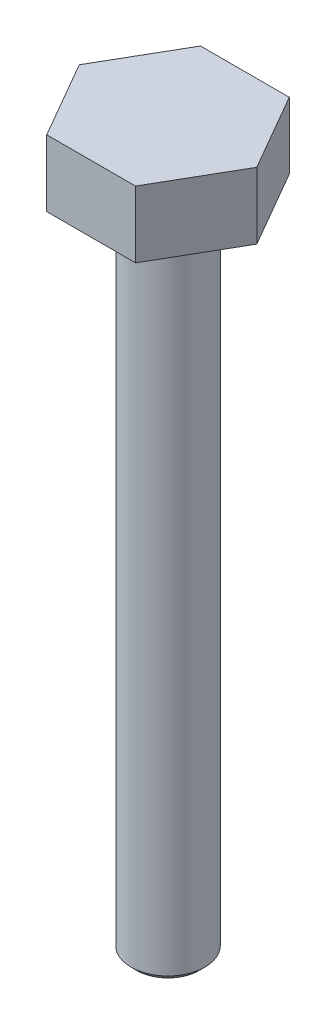
SolidWorks part; units mm, degrees
ref_plane "Front Plane" through (0, 0, 0) normal (0, 0, 1) x (1, 0, 0)
ref_plane "Top Plane" through (0, 0, 0) normal (0, 1, 0) x (1, 0, 0)
ref_plane "Right Plane" through (0, 0, 0) normal (1, 0, 0) x (0, 0, -1)
sketch "Sketch2" plane through (0, 0, 0) normal (0, 1, 0) x (1, 0, 0)
  line L1 (60.0444, 0) -> (30.0222, 52)
  line L2 (30.0222, 52) -> (-30.0222, 52)
  line L3 (-30.0222, 52) -> (-60.0444, 0)
  line L4 (-60.0444, 0) -> (-30.0222, -52)
  line L5 (-30.0222, -52) -> (30.0222, -52)
  line L6 (30.0222, -52) -> (60.0444, 0)
  circle A0 centre (0, 0) radius 52 construction
  circle A1 centre (0, 0) radius 25
  point P10 (0, 0)
  dimension "D2" = 50
  dimension "D1" = 104
extrude "Boss-Extrude1" add sketch "Sketch2" along normal blind 45 contours A1 | L1 L2 L3 L4 L5 L6
extrude "Boss-Extrude2" add sketch "Sketch2<3>" along normal blind 45 and the other way blind 445 contours A1
sketch "Sketch2<3>" plane through (0, 0, 0) normal (0, 1, 0) x (1, 0, 0) same geometry as "Sketch2"
chamfer "Chamfer1" distance 4 angle 45 1 edges at (0, -445, 25)
sketch "Sketch4" plane through (0, 45, 0) normal (0, 1, 0) x (1, 0, 0)
  line L0 (30.0222, -52) -> (60.0444, 0) construction
  circle A0 centre (0, 0) radius 52
